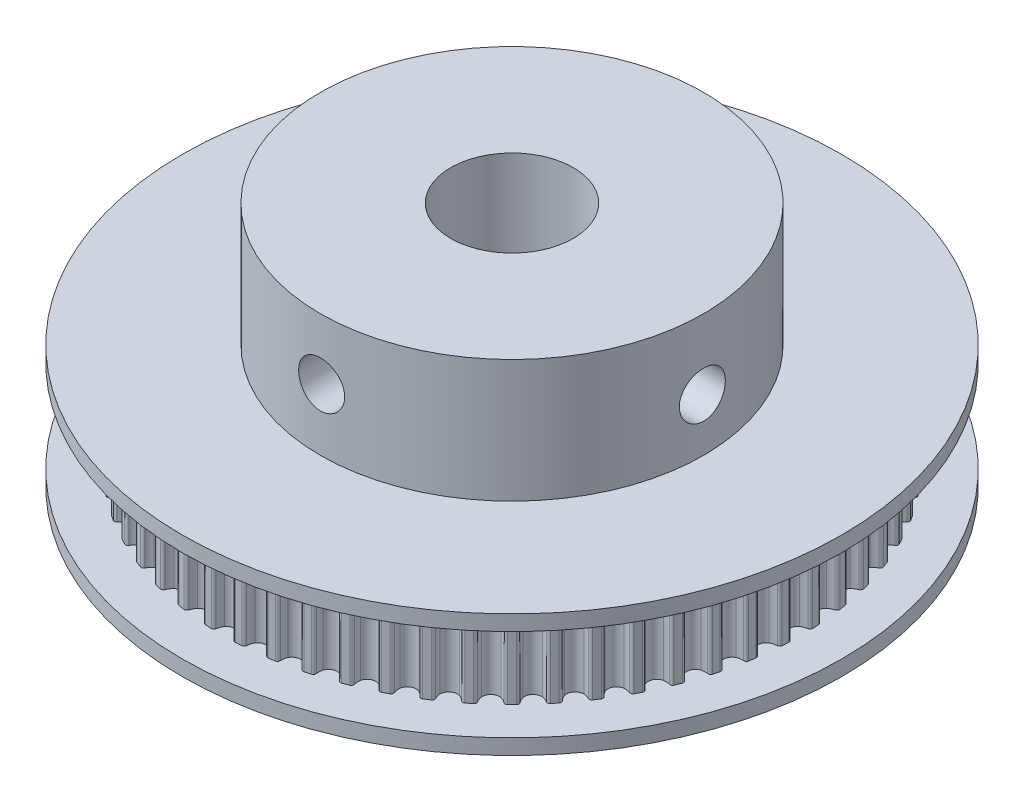
SolidWorks part; units mm, degrees
ref_plane "Front Plane" through (0, 0, 0) normal (0, 0, 1) x (1, 0, 0)
ref_plane "Top Plane" through (0, 0, 0) normal (0, 1, 0) x (1, 0, 0)
ref_plane "Right Plane" through (0, 0, 0) normal (1, 0, 0) x (0, 0, -1)
sketch "Sketch1" plane through (0, 0, 0) normal (0, 1, 0) x (1, 0, 0)
  circle A0 centre (0, 0) radius 18.8446
  dimension "D1" = 37.6892
extrude "Boss-Extrude1" add sketch "Sketch1" along normal blind 6
sketch "Sketch2" plane through (0, 6, 0) normal (0, 1, 0) x (1, 0, 0)
  line L0 (0, 0) -> (0, 18.8446) construction
  line L1 (0, 18.8446) -> (-0.4, 18.8446) construction
  line L2 (0, 18.8446) -> (0.4, 18.8446) construction
  circle A0 centre (0, 0) radius 18.8446
  circle A1 centre (0, 0) radius 18.6396 construction
  circle A2 centre (0, 0) radius 18.0846 construction
  arc A4 (-0.6199, 18.8344) -> (-0.4536, 18.2862) centre (0.4, 18.8446) ccw
  arc A5 (-0.4536, 18.2862) -> (0.4536, 18.2862) centre (0, 18.6396) ccw
  arc A6 (0.4536, 18.2862) -> (0.6199, 18.8344) centre (-0.4, 18.8446) ccw
  dimension "D1" = 37.6892
  dimension "D2" = 36.1692
  dimension "D3" = 37.2792
  dimension "D7" = 2.04
  dimension "D8" = 1.15
  dimension "D4" = 0.4
  dimension "D5" = 0.4
extrude "Cut-Extrude1" cut sketch "Sketch2" against normal blind 10 contours A5 A6 A0 A4 region at (0, 6, -18.5075)
fillet "Fillet1" radius 0.17 2 edges at (0.6199, 3, -18.8344) (-0.6199, 3, -18.8344)
ref_axis "Axis2" through (0, 6, 0) along (0, -1, 0)
pattern_circular "CirPattern2" count 60 over 360 about axis through (0, 6, 0) along (0, -1, 0) of "Cut-Extrude1", "Fillet1"
sketch "Sketch3" plane through (0, 6, 0) normal (0, 1, 0) x (1, 0, 0)
  circle A0 centre (0, 0) radius 21.5
  dimension "D1" = 43
extrude "Boss-Extrude2" add sketch "Sketch3" along normal blind 1
sketch "Sketch4" plane through (0, 0, 0) normal (0, -1, 0) x (1, 0, 0)
  circle A0 centre (0, 0) radius 21.5
  dimension "D1" = 43
extrude "Boss-Extrude3" add sketch "Sketch4" along normal blind 1
sketch "Sketch5" plane through (0, 7, 0) normal (0, 1, 0) x (1, 0, 0)
  circle A0 centre (0, 0) radius 12.5
  circle A1 centre (0, 0) radius 4
  dimension "D1" = 25
  dimension "D2" = 8
extrude "Boss-Extrude4" add sketch "Sketch5" along normal blind 8
sketch "Sketch6" plane through (0, 7, 0) normal (0, 1, 0) x (1, 0, 0)
  circle A0 centre (0, 0) radius 4
  dimension "D1" = 8
extrude "Cut-Extrude2" cut sketch "Sketch6" against normal through all
ref_plane "Plane1" through (12.5, 0, 0) normal (1, 0, 0) x (0, 0, -1)
sketch "Sketch7" plane through (12.5, 0, 0) normal (1, 0, 0) x (0, 0, -1)
  circle A0 centre (0, 10.4298) radius 1.5
  point P2 (0, 10.4298)
  dimension "D1" = 3
extrude "Cut-Extrude3" cut sketch "Sketch7" against normal up to next
ref_plane "Plane2" through (0, 0, 12.5) normal (0, 0, 1) x (1, 0, 0)
sketch "Sketch8" plane through (0, 0, 12.5) normal (0, 0, 1) x (1, 0, 0)
  circle A0 centre (0, 11.0138) radius 1.5
  point P2 (0, 11.0138)
  dimension "D1" = 3
extrude "Cut-Extrude4" cut sketch "Sketch8" against normal up to next
equation "\"GD\"= 0.76mm"
equation "\"SBD\"= 2mm"
equation "\"NT\"= 60"
equation "\"PD\"= ( \"SBD\" * \"NT\" ) / 3.14159"
equation "\"U\"= 0.254mm"
equation "\"OD\"= \"PD\" - ( 2 * \"U\" )"
equation "\"RD\"= \"OD\" - ( 2 * \"GD\" )"
equation "\"R3\"= 0.555mm"
equation "\"R2\"= 1mm"
equation "\"R1\"= 0.15mm"
equation "\"DT\"= 0.02mm"
equation "\"b\"= 0.4mm"
equation "\"D1@Sketch1\"= \"OD\""
equation "\"D1@Sketch2\"= \"OD\""
equation "\"D3@Sketch2\"= \"RD\" + \"R3\" * 2"
equation "\"D2@Sketch2\"= \"RD\""
equation "\"D4@Sketch2\"= \"b\""
equation "\"D5@Sketch2\"= \"b\""
equation "\"D7@Sketch2\"= ( \"R2\" + \"DT\" ) * 2"
equation "\"D8@Sketch2\"= ( \"R3\" + \"DT\" ) * 2"
equation "\"D1@Fillet1\"=\"R1\"+\"DT\""
equation "\"D1@CirPattern2\"=\"NT\""
